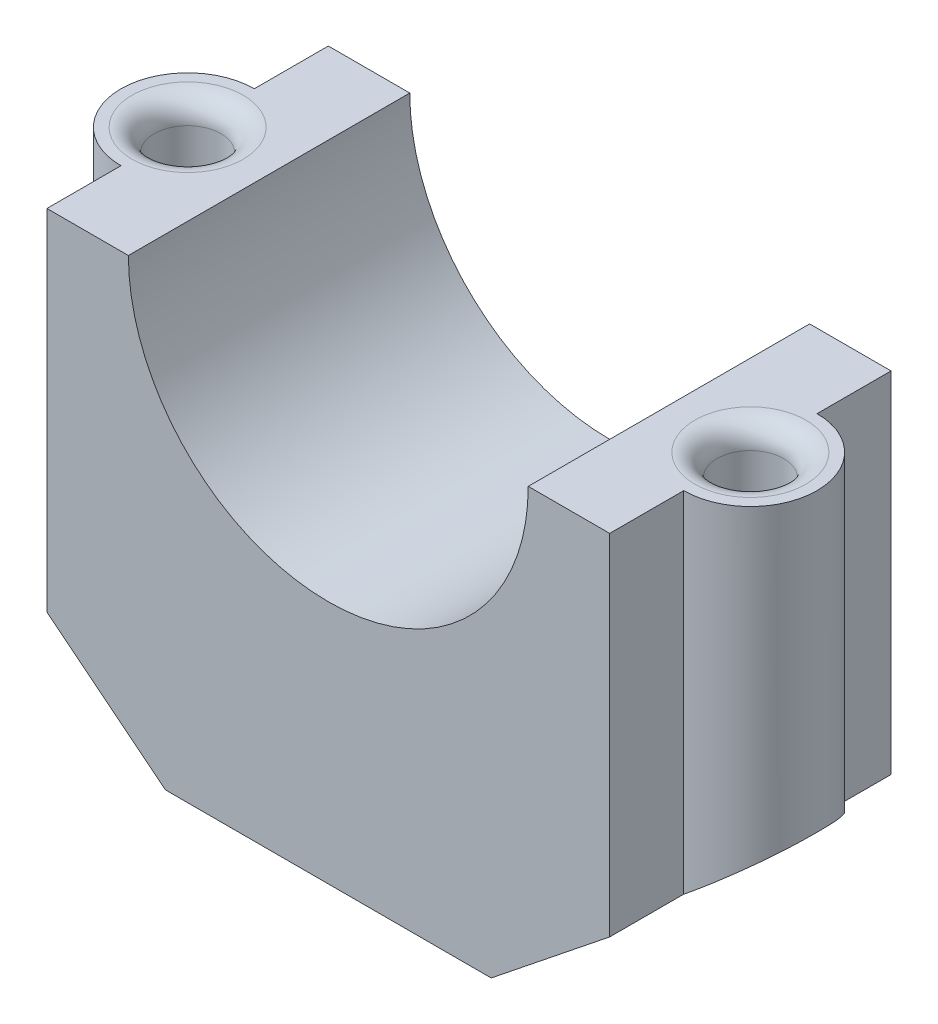
SolidWorks part; units mm, degrees
ref_plane "Front Plane" through (0, 0, 0) normal (0, 0, 1) x (1, 0, 0)
ref_plane "Top Plane" through (0, 0, 0) normal (0, 1, 0) x (1, 0, 0)
ref_plane "Right Plane" through (0, 0, 0) normal (1, 0, 0) x (0, 0, -1)
sketch "Sketch1" plane through (0, 0, 0) normal (0, 0, 1) x (1, 0, 0)
  line L0 (-22, -60) -> (22, -60)
  line L1 (-47, -40) -> (-22, -60)
  line L2 (47, 0) -> (47, -40)
  line L3 (47, -40) -> (22, -60)
  line L4 (0, 82.9747) -> (0, -98.0972) construction
  line L5 (27, 0) -> (47, 0)
  line L6 (-47, 0) -> (-47, -40)
  line L7 (-27, 0) -> (-47, 0)
  arc A1 (-27, 0) -> (27, 0) centre (0, 0) ccw
  point P8 (0, -60)
  dimension "D2" = 54
  dimension "D3" = 60
  dimension "D4" = 47
  dimension "D5" = 40
  dimension "D6" = 25
extrude "Boss-Extrude1" add sketch "Sketch1" along normal mid plane 38
sketch "Sketch3" plane through (0, 0, 0) normal (0, 1, 0) x (1, 0, 0)
  line L0 (47, -19) -> (47, 19) construction
  line L1 (-47, -19) -> (-47, 19) construction
  line L2 (47, -19) -> (27, -19) construction
  line L3 (-38, 19) -> (38, 19)
  line L4 (-38, 19) -> (-38, 9)
  line L5 (-38, -19) -> (38, -19)
  line L6 (38, 19) -> (38, 9)
  line L7 (-38, 19) -> (38, -19) construction
  line L8 (-38, -19) -> (38, 19) construction
  line L9 (-38, -9) -> (-38, -19)
  line L10 (-47, 19) -> (47, 19)
  line L11 (-47, 19) -> (-47, -19)
  line L12 (-47, -19) -> (47, -19)
  line L13 (47, 19) -> (47, -19)
  line L14 (-47, 19) -> (47, -19) construction
  line L15 (-47, -19) -> (47, 19) construction
  line L16 (38, -9) -> (38, -19)
  circle A0 centre (38, 0) radius 4.5
  circle A1 centre (-38, 0) radius 4.5
  circle A2 centre (38, 0) radius 9
  circle A3 centre (-38, 0) radius 9
  point P11 (0, 0)
  point P18 (0, 0)
  line M1 (47, 19) -> (27, 19)
  line M3 (27, -19) -> (47, -19)
  line M4 (47, -19) -> (47, 19)
  dimension "D1" = 18
  dimension "D2" = 18
  dimension "D3" = 9
  dimension "D4" = 9
extrude "Cut-Extrude1" cut sketch "Sketch3" against normal up to next contours A1 | A0 | A2 L13 L6 M1 | A2 L16 M3 M4 | A3 L4 L10 L11 | A3 L11 L12 L9 region at (-42.903, 0, -12.8652) region at (42.903, 0, -12.8652) region at (-42.903, 0, 12.8652) region at (42.903, 0, 12.8652) region at (38, 0, 0) region at (-38, 0, 0)
fillet "Fillet1" radius 3 4 edges at (42.5, -43.6, 0) (33.5, 0, 0) (-42.5, 0, 0) (-42.5, -43.6, 0)
